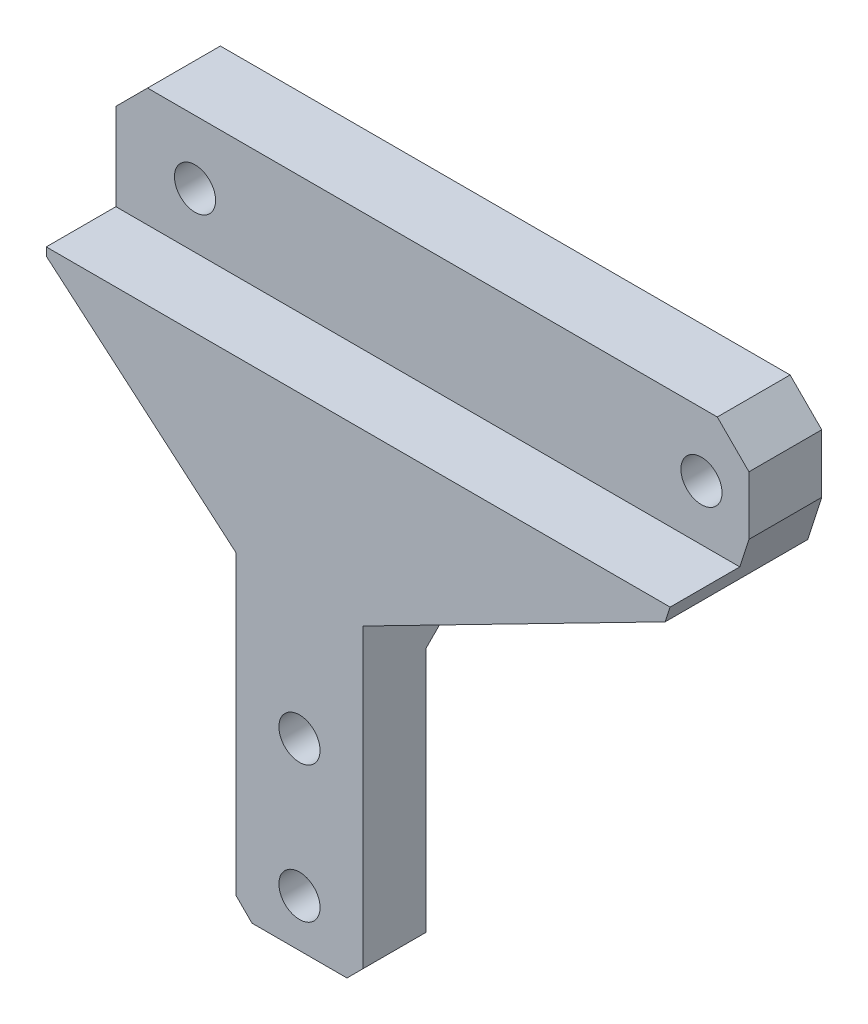
SolidWorks part; units mm, degrees
ref_plane "前视基准面" through (0, 0, 0) normal (0, 0, 1) x (1, 0, 0)
ref_plane "上视基准面" through (0, 0, 0) normal (0, 1, 0) x (1, 0, 0)
ref_plane "右视基准面" through (0, 0, 0) normal (1, 0, 0) x (0, 0, -1)
other "Configuration Table"
sketch "草图1" plane through (0, 0, 0) normal (0, 0, 1) x (1, 0, 0)
  line L1 (-10, 2) -> (10, 2)
  line L2 (-10, 2) -> (-10, -2)
  line L4 (10, 2) -> (10, -2)
  line L5 (-10, 2) -> (10, -2) construction
  line L6 (-10, -2) -> (10, 2) construction
  line L8 (-4, -7.1203) -> (-4, -17)
  line L9 (-4, -17) -> (0, -17)
  line L10 (0, -7.1203) -> (0, -17)
  line L11 (-10, -2) -> (-4, -7.1203)
  line L12 (0, -7.1203) -> (10, -2)
  circle A0 centre (-7.5, 0) radius 0.65
  circle A1 centre (8.5, 0) radius 0.65
  circle A2 centre (-2, -15.5) radius 0.65
  circle A3 centre (-2, -11.2) radius 0.65
  point P0 (0, 0)
  dimension "D5" = 1.3
  dimension "D7" = 1.3
  dimension "D12" = 1.3
  dimension "D13" = 1.3
  dimension "D1" = 20
  dimension "D2" = 4
  dimension "D3" = 4
  dimension "D6" = 2.5
  dimension "D8" = 1.5
  dimension "D9" = 10
  dimension "D10" = 2
  dimension "D11" = 2
  dimension "D14" = 2
  dimension "D15" = 2
  dimension "D16" = 1.5
  dimension "D17" = 4.3
extrude "凸台-拉伸2" add sketch "草图1" along normal blind 5.5
sketch "草图3" plane through (0, 0, 0) normal (0, 0, -1) x (-1, 0, 0)
  line L0 (0, -7.7252) -> (4, -7.7252)
  line L8 (-10, 2) -> (-10, -2)
  line L9 (-10, -2) -> (0, -7.1203)
  line L10 (0, -7.1203) -> (0, -17)
  line L11 (0, -17) -> (4, -17)
  line L12 (4, -17) -> (4, -7.1203)
  line L14 (10, -2) -> (10, 2)
  line L15 (10, 2) -> (-10, 2)
  line L18 (0, -7.7252) -> (0, -17)
  line L19 (0, -17) -> (4, -17)
  line L20 (4, -17) -> (4, -7.7252)
  line L25 (4, -7.1203) -> (10, -2)
  circle A0 centre (2, -15.5) radius 0.65 construction
  circle A1 centre (2, -11.2) radius 0.65 construction
  circle A2 centre (2, -15.5) radius 0.65
  circle A3 centre (2, -11.2) radius 0.65
  dimension "D1" = 0
extrude "切除-拉伸2" cut sketch "草图3" against normal blind 3.5
chamfer "倒角1" distance 1 angle 45 1 edges at (-2, -7.7252, 3.5)
chamfer "倒角2" distance 1 angle 45 2 edges at (-10, 2, 2.75) (10, 2, 2.75)
chamfer "倒角3" distance 0.5 angle 45 2 edges at (-4, -17, 4.5) (0, -17, 4.5)
sketch "草图4" plane through (0, 0, 5.5) normal (0, 0, 1) x (1, 0, 0)
  line L6 (-10, -1.7462) -> (10, -1.7462)
  line L12 (-4, -7.1203) -> (-4, -16.5)
  line L13 (-4, -16.5) -> (-3.5, -17)
  line L14 (-3.5, -17) -> (-0.5, -17)
  line L15 (-0.5, -17) -> (0, -16.5)
  line L16 (0, -16.5) -> (0, -7.1203)
  line L17 (0, -7.1203) -> (10, -2)
  line L18 (10, -2) -> (10, 1)
  line L19 (10, 1) -> (9, 2)
  line L20 (9, 2) -> (-9, 2)
  line L21 (-9, 2) -> (-10, 1)
  line L22 (-10, 1) -> (-10, -2)
  line L23 (-10, -2) -> (-4, -7.1203)
  line L30 (10, -1.7462) -> (10, 1)
  line L31 (10, 1) -> (9, 2)
  line L32 (9, 2) -> (-9, 2)
  line L33 (-9, 2) -> (-10, 1)
  line L34 (-10, 1) -> (-10, -1.7462)
  circle A0 centre (8.5, 0) radius 0.65 construction
  circle A1 centre (-7.5, 0) radius 0.65 construction
  circle A2 centre (8.5, 0) radius 0.65
  circle A3 centre (-7.5, 0) radius 0.65
  dimension "D1" = 0
extrude "切除-拉伸3" cut sketch "草图4" against normal blind 2.2
chamfer "倒角4" distance 0.5 angle 45 1 edges at (10, -2, 2.75) first distance on face at (5, -4.5601, 2.75)
sketch "草图5" plane through (0, 0, 0) normal (0, 0, -1) x (-1, 0, 0)
  line L11 (-10, 1) -> (-10, -0.8488)
  line L12 (-10, -0.8488) -> (-9.5549, -2.2279)
  line L13 (-9.5549, -2.2279) -> (0, -7.1203)
  line L14 (0, -7.1203) -> (0, -7.7252)
  line L15 (0, -7.7252) -> (4, -7.7252)
  line L16 (4, -7.7252) -> (4, -7.1203)
  line L17 (4, -7.1203) -> (10, -2)
  line L18 (10, -2) -> (10, 1)
  line L19 (10, 1) -> (9, 2)
  line L20 (9, 2) -> (-9, 2)
  line L21 (-9, 2) -> (-10, 1)
  line L22 (-10, 1) -> (-10, -0.8488)
  line L23 (-10, -0.8488) -> (-9.5549, -2.2279)
  line L24 (-9.5549, -2.2279) -> (0, -7.1203)
  line L25 (0, -7.1203) -> (0, -7.7252)
  line L26 (0, -7.7252) -> (4, -7.7252)
  line L27 (4, -7.7252) -> (4, -7.1203)
  line L28 (4, -7.1203) -> (10, -2)
  line L29 (10, -2) -> (10, 1)
  line L30 (10, 1) -> (9, 2)
  line L31 (9, 2) -> (-9, 2)
  line L32 (-9, 2) -> (-10, 1)
  circle A0 centre (7.5, 0) radius 0.65 construction
  circle A1 centre (-8.5, 0) radius 0.65 construction
  circle A2 centre (7.5, 0) radius 0.65
  circle A3 centre (-8.5, 0) radius 0.65
  dimension "D1" = 0
extrude "切除-拉伸4" cut sketch "草图5" against normal blind 1
